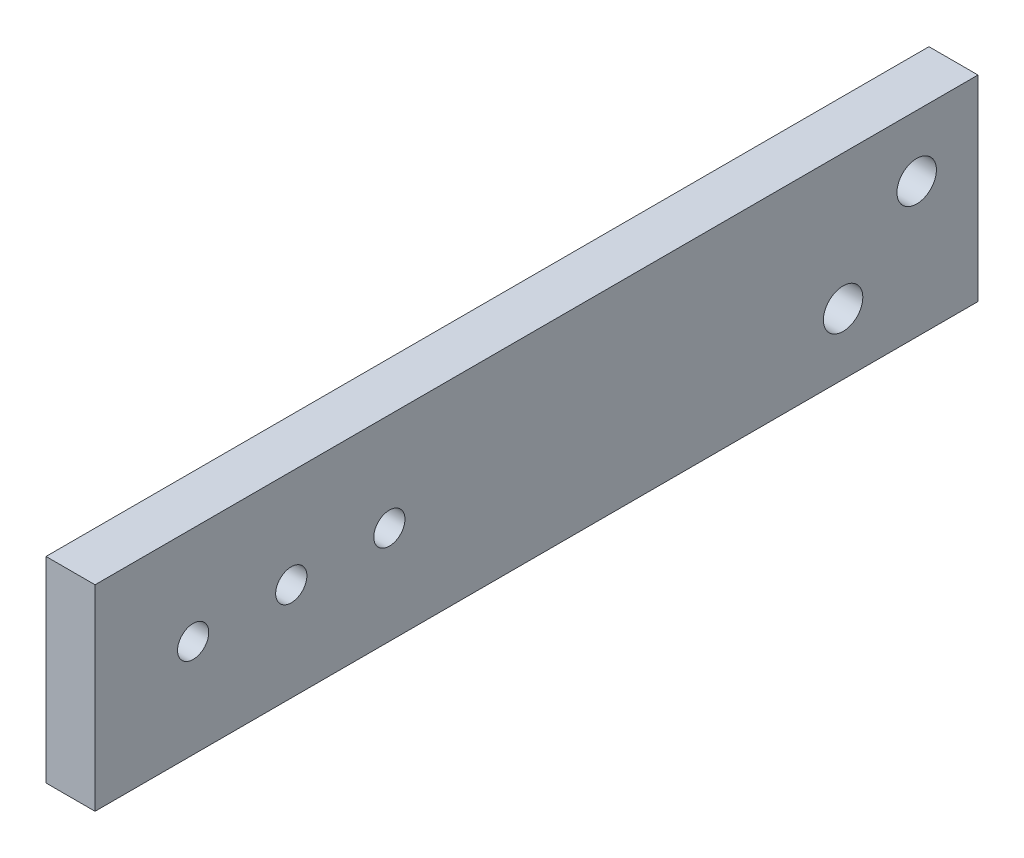
SolidWorks part; units mm, degrees
material "6061-T6 (SS)"
ref_plane "Front" through (0, 0, 0) normal (0, 0, 1) x (1, 0, 0)
ref_plane "Top" through (0, 0, 0) normal (0, 1, 0) x (1, 0, 0)
ref_plane "Right" through (0, 0, 0) normal (1, 0, 0) x (0, 0, -1)
sketch "Sketch1" plane through (0, 0, 0) normal (1, 0, 0) x (0, 0, -1)
  line L1 (0, 0) -> (114.3, 0)
  line L2 (0, 0) -> (0, 25.4)
  line L3 (0, 25.4) -> (114.3, 25.4)
  line L6 (114.3, 25.4) -> (114.3, 0)
  dimension "D1" = 25.4
  dimension "D2" = 114.3
extrude "Boss-Extrude1" add sketch "Sketch1" along normal blind 6.35
hole_wizard "#10-32 Tapped Hole1" positions "Sketch2" profile "Sketch3" tap size "#10-32" standard "ANSI Inch" end condition through all
sketch "Sketch2" plane through (6.35, 0, 0) normal (1, 0, 0) x (0, 0, -1)
  line L0 (0, 0) -> (12.7, 12.7) construction
  line L1 (12.7, 12.7) -> (25.4, 12.7) construction
  line L2 (25.4, 12.7) -> (38.1, 12.7) construction
  line L3 (38.1, 12.7) -> (50.8, 25.4) construction
  line L4 (114.3, 25.4) -> (0, 25.4) construction
  line L6 (0, 25.4) -> (0, 0) construction
  point P0 (12.7, 12.7)
  point P2 (25.4, 12.7)
  point P4 (38.1, 12.7)
  dimension "D1" = 50.8
  dimension "D2" = 12.7
sketch "Sketch3" plane through (6.35, 12.7, -12.7) normal (0, 1, 0) x (0, 0, -1)
  line L0 (0, 0) -> (0, 6.35)
  line L1 (0, 6.35) -> (2.0193, 6.35)
  line L2 (2.0193, 6.35) -> (2.0193, 0)
  line L5 (2.0193, 0) -> (0, 0)
  line L11 (0, -6.35) -> (0, 107.95) construction
  dimension "Thru Tap Drill Dia." = 4.0386
  dimension "Thru Tap Drill Depth" = 6.35
cosmetic thread "Hole Thread1"
cosmetic thread "Hole Thread2"
cosmetic thread "Hole Thread3"
hole_wizard "#10 Clearance Hole1" positions "Sketch4" profile "Sketch5" hole size "#10" standard "ANSI Inch" end condition through all
sketch "Sketch4" plane through (6.35, 0, 0) normal (1, 0, 0) x (0, 0, -1)
  line L0 (88.9, 0) -> (96.8375, 7.9375) construction
  line L1 (0, 0) -> (114.3, 0) construction
  line L2 (96.8375, 7.9375) -> (106.3625, 17.4625) construction
  line L3 (106.3625, 17.4625) -> (114.3, 25.4) construction
  line L5 (114.3, 0) -> (114.3, 25.4) construction
  point P13 (106.3625, 17.4625)
  point P15 (96.8375, 7.9375)
  dimension "D1" = 25.4
  dimension "D2" = 9.525
sketch "Sketch5" plane through (6.35, 17.4625, -106.3625) normal (0, 1, 0) x (0, 0, -1)
  line L0 (0, 0) -> (0, 6.35)
  line L1 (0, 6.35) -> (2.5527, 6.35)
  line L2 (2.5527, 6.35) -> (2.5527, 0)
  line L5 (2.5527, 0) -> (0, 0)
  line L11 (0, -6.35) -> (0, 107.95) construction
  dimension "Thru Hole Dia." = 5.1054
  dimension "Thru Hole Depth" = 6.35
